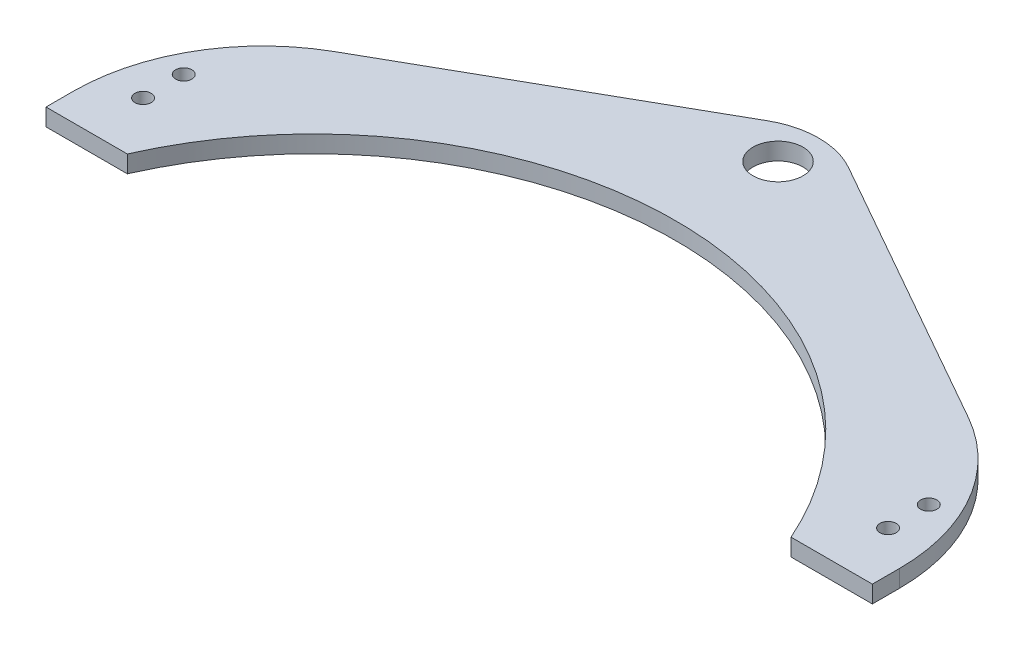
SolidWorks part; units mm, degrees
ref_plane "Front Plane" through (0, 0, 0) normal (0, 0, 1) x (1, 0, 0)
ref_plane "Top Plane" through (0, 0, 0) normal (0, 1, 0) x (1, 0, 0)
ref_plane "Right Plane" through (0, 0, 0) normal (1, 0, 0) x (0, 0, -1)
sketch "Sketch1" plane through (0, 0, 0) normal (0, 1, 0) x (1, 0, 0)
  line L0 (0, 0) -> (122.4, 0)
  line L1 (61.2, 0) -> (61.2, 39.9)
  line L2 (122.4, 0) -> (137.4, 0)
  line L3 (0, 0) -> (-15, 0)
  line L4 (137.4, 0) -> (137.4, 16.6577)
  line L5 (-15, 0) -> (-15, 16.6577)
  line L6 (61.2, 0) -> (61.2, 58.8)
  line L7 (61.2, 58.8) -> (61.2, 66.3)
  line L8 (61.2, 66.3) -> (61.2465, 66.3)
  line L9 (61.2, 66.3) -> (61.1535, 66.3)
  line L10 (68.6399, 64.3514) -> (129.7934, 29.709)
  line L11 (53.7601, 64.3514) -> (-7.3934, 29.709)
  line L12 (129.9, 0) -> (129.9, 10.4)
  line L13 (129.9, 10.4) -> (129.9, 17.9)
  line L14 (-7.5, 0) -> (-7.5, 10.4)
  line L15 (119.6512, 35.4544) -> (68.6399, 64.3514)
  line L16 (137.4, 5.0012) -> (137.4, 0)
  line L17 (53.7601, 64.3514) -> (2.7488, 35.4544)
  line L18 (-15, 5.0012) -> (-15, 0)
  line L19 (-7.5, 10.4) -> (-7.5, 17.9)
  arc A0 (0, 0) -> (122.4, 0) centre (61.2, -26.9726) cw
  circle A1 centre (61.2, 58.8) radius 4.6
  arc A2 (61.2465, 66.3) -> (68.6399, 64.3514) centre (61.2465, 51.3) cw
  arc A3 (61.1535, 66.3) -> (53.7601, 64.3514) centre (61.1535, 51.3) ccw
  arc A4 (-15, 16.6577) -> (-7.3934, 29.709) centre (0, 16.6577) cw
  arc A5 (137.4, 16.6577) -> (129.7934, 29.709) centre (122.4, 16.6577) ccw
  circle A6 centre (129.9, 17.9) radius 1.5
  circle A7 centre (129.9, 10.4) radius 1.5
  arc A10 (119.6512, 35.4544) -> (137.4, 5.0012) centre (102.4, 5.0012) cw
  arc A11 (2.7488, 35.4544) -> (-15, 5.0012) centre (20, 5.0012) ccw
  circle A13 centre (-7.5, 17.9) radius 1.5
  circle A14 centre (-7.5, 10.4) radius 1.5
  point P17 (65.2, 66.3)
  point P20 (57.2, 66.3)
  point P23 (-15, 25.4)
  point P26 (137.4, 25.4)
  point P41 (137.4, 25.4)
  point P44 (-15, 25.4)
  dimension "D8" = 7.5
  dimension "D11" = 15
  dimension "D12" = 15
  dimension "D15" = 10.4
  dimension "D16" = 35
  dimension "D17" = 7.5
  dimension "D1" = 122.4
  dimension "D2" = 39.9
  dimension "D3" = 15
  dimension "D4" = 15
  dimension "D5" = 25.4
  dimension "D6" = 25.4
  dimension "D7" = 58.8
  dimension "D9" = 4
  dimension "D10" = 4
  dimension "D13" = 10.4
  dimension "D14" = 7.5
extrude "Boss-Extrude2" add sketch "Sketch1" along normal blind 3.175 contours L11 A11 L5 L3 A13 A0 L6 A1 L7 L9 A3 | A10 L10 A2 L8 L7 A1 L6 A0 L2 A7 A6 L4 region at (21.8428, 0, -33.4988) region at (100.5572, 0, -33.4988)
